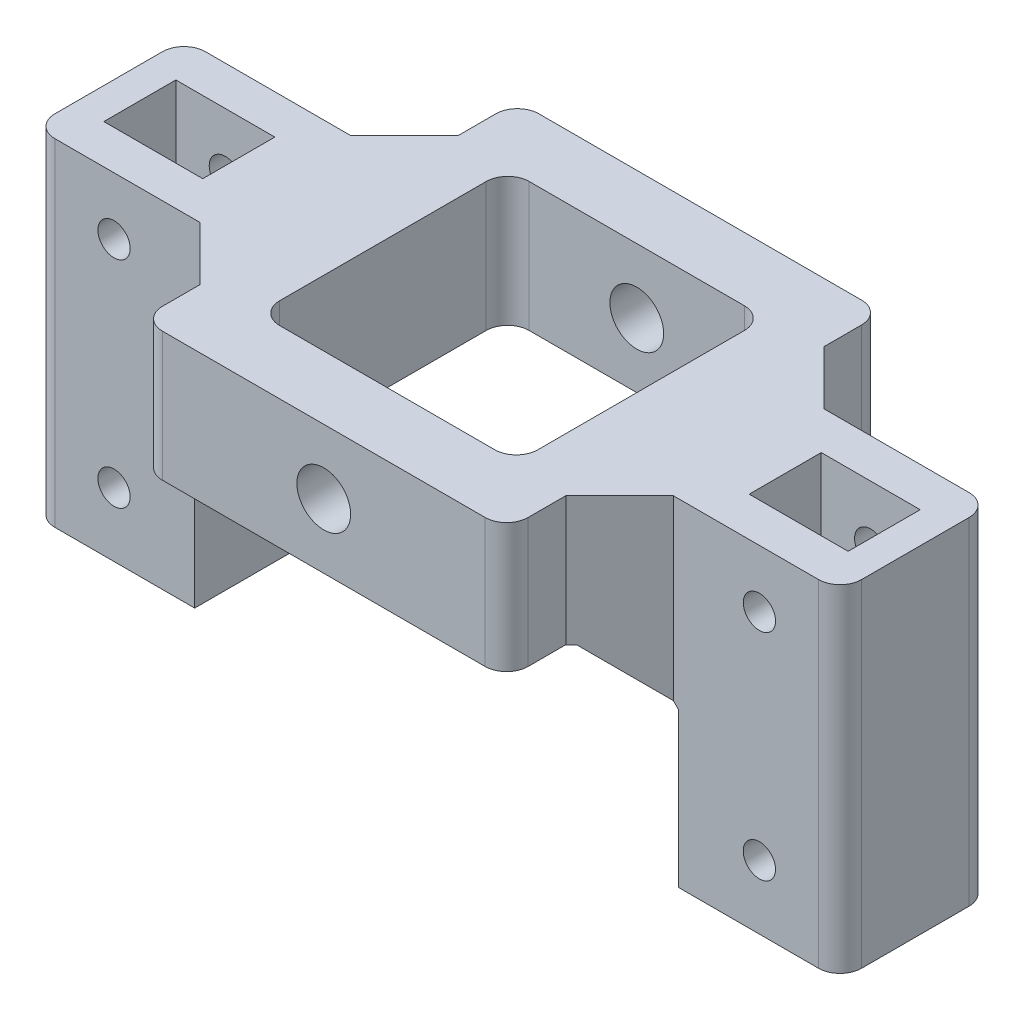
SolidWorks part; units mm, degrees
material "聚脂树脂"
ref_plane "前视基准面" through (0, 0, 0) normal (0, 0, 1) x (1, 0, 0)
ref_plane "上视基准面" through (0, 0, 0) normal (0, 1, 0) x (1, 0, 0)
ref_plane "右视基准面" through (0, 0, 0) normal (1, 0, 0) x (0, 0, -1)
other "Configuration Table"
sketch "草图1" plane through (0, 0, 0) normal (0, 0, 1) x (1, 0, 0)
  line L0 (0, 0) -> (63.4535, 0) construction
  line L5 (-22.5, 17.15) -> (-37.5, -17.15) construction
  line L6 (22.5, -17.15) -> (37.5, -17.15)
  line L7 (0, 0) -> (0, 35.1803) construction
  line L8 (22.5, -17.15) -> (22.5, 17.15)
  line L9 (22.5, 17.15) -> (37.5, 17.15)
  line L10 (37.5, -17.15) -> (37.5, 17.15)
  line L11 (22.5, -17.15) -> (37.5, 17.15) construction
  line L12 (22.5, 17.15) -> (37.5, -17.15) construction
  line L13 (-22.5, -17.15) -> (-37.5, 17.15) construction
  line L14 (-37.5, -17.15) -> (-37.5, 17.15)
  line L15 (-22.5, 17.15) -> (-37.5, 17.15)
  line L16 (-22.5, -17.15) -> (-22.5, 17.15)
  line L17 (-22.5, -17.15) -> (-37.5, -17.15)
  point P0 (30, 0)
  point P21 (-30, 0)
  dimension "D3" = 30
  dimension "D1" = 15
  dimension "D2" = 34.3
extrude "凸台-拉伸1" add sketch "草图1" along normal blind 7 and the other way blind 7
sketch "草图2" plane through (0, 17.15, 0) normal (0, 1, 0) x (1, 0, 0)
  line L0 (0, 0) -> (0, 28.9204) construction
  line L1 (0, 0) -> (49.6088, 0) construction
  line L2 (-25.4, 3.35) -> (-34.6, -3.35) construction
  line L3 (25.4, -3.35) -> (34.6, -3.35)
  line L4 (25.4, -3.35) -> (25.4, 3.35)
  line L5 (25.4, 3.35) -> (34.6, 3.35)
  line L6 (34.6, -3.35) -> (34.6, 3.35)
  line L7 (25.4, -3.35) -> (34.6, 3.35) construction
  line L8 (25.4, 3.35) -> (34.6, -3.35) construction
  line L9 (-25.4, -3.35) -> (-34.6, 3.35) construction
  line L10 (-34.6, -3.35) -> (-34.6, 3.35)
  line L11 (-25.4, 3.35) -> (-34.6, 3.35)
  line L12 (-25.4, -3.35) -> (-25.4, 3.35)
  line L13 (-25.4, -3.35) -> (-34.6, -3.35)
  point P3 (30, 0)
  point P13 (-30, 0)
  dimension "D1" = 9.2
  dimension "D2" = 6.7
  dimension "D3" = 30
extrude "切除-拉伸1" cut sketch "草图2" against normal blind 62
sketch "草图3" plane through (0, 17.15, 0) normal (0, 1, 0) x (1, 0, 0)
  line L0 (0, 0) -> (46.7542, 0) construction
  line L1 (0, 0) -> (0, 26.73) construction
  line L2 (22.5, 7) -> (17, 7)
  line L3 (17, 7) -> (17, 17.5)
  line L4 (17, 17.5) -> (-17, 17.5)
  line L6 (-12, 11.6) -> (12, 11.6)
  line L7 (12, 11.6) -> (12, -11.6)
  line L8 (22.5, 7) -> (22.5, -7)
  line L9 (22.5, 7) -> (22.5, -7) construction
  line L10 (-12, -11.6) -> (12, -11.6)
  line L12 (17, -17.5) -> (-17, -17.5)
  line L13 (17, -7) -> (17, -17.5)
  line L14 (22.5, -7) -> (17, -7)
  line L15 (-22.5, -7) -> (-17, -7)
  line L16 (-17, -7) -> (-17, -17.5)
  line L17 (-22.5, 7) -> (-22.5, -7)
  line L18 (-12, 11.6) -> (-12, -11.6)
  line L19 (-17, 7) -> (-17, 17.5)
  line L20 (-22.5, 7) -> (-17, 7)
  point P16 (22.5, 0)
  point P17 (12, 0)
  point P24 (0, -17.5)
  point P25 (0, -11.6)
  point P27 (0, 11.6)
  point P28 (0, 17.5)
  point P29 (-12, 0)
  point P30 (-22.5, 0)
  dimension "D1" = 23.2
  dimension "D2" = 24
  dimension "D3" = 34
  dimension "D4" = 35
extrude "凸台-拉伸2" add sketch "草图3" against normal blind 12
sketch "草图4" plane through (0, 0, 17.5) normal (0, 0, 1) x (1, 0, 0)
  line L0 (0, 0) -> (0, 29.922) construction
  line L1 (-17, 5.15) -> (17, 5.15) construction
  circle A0 centre (0, 11.15) radius 2.5
  dimension "D1" = 5
  dimension "D2" = 6
extrude "切除-拉伸2" cut sketch "草图4" against normal blind 90
sketch "草图6" plane through (0, 0, 7) normal (0, 0, 1) x (1, 0, 0)
  line L0 (0, 0) -> (0, 28.8184) construction
  line L1 (0, 0) -> (51.072, 0) construction
  line L2 (-37.5, 17.15) -> (-37.5, 29.15)
  line L3 (-37.5, 29.15) -> (-22.5, 29.15)
  line L4 (-22.5, 29.15) -> (-22.5, 17.15)
  line L5 (-37.5, 17.15) -> (-17, 17.15) construction
  line L7 (-35, 17.15) -> (-35, 26.65)
  line L8 (-35, 26.65) -> (-25, 26.65)
  line L9 (-25, 26.65) -> (-25, 17.15)
  line L10 (-37.5, 17.15) -> (-35, 17.15)
  line L11 (-25, 17.15) -> (-22.5, 17.15)
  line L12 (25, 26.65) -> (25, 17.15)
  line L13 (35, 26.65) -> (25, 26.65)
  line L14 (35, 17.15) -> (35, 26.65)
  line L15 (37.5, 17.15) -> (35, 17.15)
  line L16 (37.5, 17.15) -> (37.5, 29.15)
  line L17 (37.5, 29.15) -> (22.5, 29.15)
  line L18 (22.5, 29.15) -> (22.5, 17.15)
  line L19 (25, 17.15) -> (22.5, 17.15)
  dimension "D1" = 12
  dimension "D2" = 2.5
fillet "圆角1" radius 2 4 edges at (37.5, 0, -7) (37.5, 0, 7) (-37.5, 0, -7) (-37.5, 0, 7)
chamfer "倒角1" distance 5 angle 45 2 edges at (22.5, 5.15, 0) (-22.5, 5.15, 0)
chamfer "倒角2" distance 5 angle 45 4 edges at (17, 11.15, -7) (-17, 11.15, -7) (17, 11.15, 7) (-17, 11.15, 7)
fillet "圆角2" radius 2 8 edges at (17, 11.15, 17.5) (-17, 11.15, 17.5) (-17, 11.15, -17.5) (17, 11.15, -17.5) (-12, 11.15, 11.6) (12, 11.15, 11.6) (12, 11.15, -11.6) (-12, 11.15, -11.6)
sketch "草图7" plane through (0, 0, 7) normal (0, 0, 1) x (1, 0, 0)
  line L0 (0, 0) -> (0, 26.3753) construction
  line L1 (0, 1.8) -> (49.2666, 1.8) construction
  line L2 (0, 0) -> (53.2402, 0) construction
  circle A0 centre (30, 11.8) radius 1.5
  circle A1 centre (30, -8.2) radius 1.5
  circle A2 centre (-30, -8.2) radius 1.5
  circle A3 centre (-30, 11.8) radius 1.5
  dimension "D1" = 60
  dimension "D2" = 20
  dimension "D3" = 3
  dimension "D4" = 1.8
extrude "切除-拉伸3" cut sketch "草图7" against normal blind 34
sketch "草图9" plane through (0, 0, 7) normal (0, 0, 1) x (1, 0, 0)
  line L0 (-22.5, -14.15) -> (-22.5, -17.15)
  line L1 (-22.5, -17.15) -> (-22.5, 0.15) construction
  line L2 (-22.5, -17.15) -> (-37.5, -17.15)
  line L3 (-37.5, -17.15) -> (-37.5, -14.15)
  line L4 (-37.5, -17.15) -> (-37.5, 17.15) construction
  line L5 (-37.5, -14.15) -> (-22.5, -14.15)
  line L6 (0, 0) -> (0, -19.4283) construction
  line L7 (37.5, -17.15) -> (37.5, -14.15)
  line L8 (22.5, -17.15) -> (37.5, -17.15)
  line L9 (22.5, -14.15) -> (22.5, -17.15)
  line L10 (37.5, -14.15) -> (22.5, -14.15)
  dimension "D1" = 3
extrude "切除-拉伸4" cut sketch "草图9" against normal blind 34
equation "\"5】\"=10"
